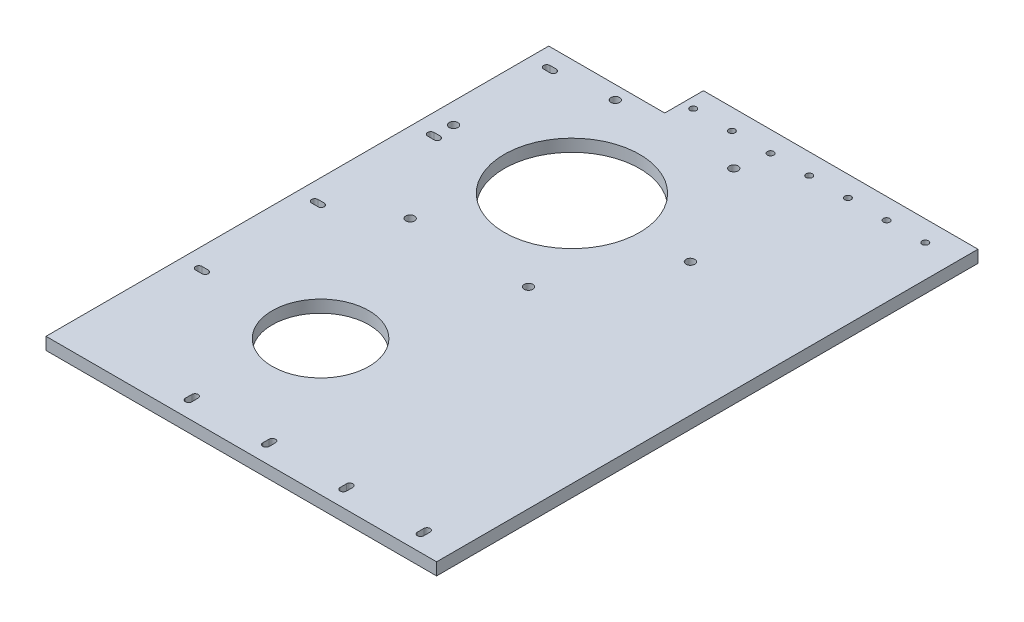
SolidWorks part; units mm, degrees
ref_plane "Front Plane" through (0, 0, 0) normal (0, 0, 1) x (1, 0, 0)
ref_plane "Top Plane" through (0, 0, 0) normal (0, 1, 0) x (1, 0, 0)
ref_plane "Right Plane" through (0, 0, 0) normal (1, 0, 0) x (0, 0, -1)
sketch "Sketch1" plane through (0, 0, 0) normal (0, 1, 0) x (1, 0, 0)
  line L3 (-71, 140) -> (71, 140)
  line L4 (71, -140) -> (71, 140)
  line L5 (0, 140) -> (0, -135) construction
  line L6 (0, 0) -> (71, 0) construction
  line L10 (-71, 140) -> (-71, 120)
  line L11 (-71, 120) -> (-131, 120)
  line L12 (-131, 120) -> (-131, -140)
  line L13 (-131, -140) -> (71, -140)
  point P0 (0, 0)
  dimension "D1" = 280
  dimension "D2" = 20
  dimension "D3" = 202
  dimension "D4" = 60
extrude "Boss-Extrude1" add sketch "Sketch1" along normal blind 6.35
sketch "Sketch2" plane through (0, 6.35, 0) normal (0, 1, 0) x (1, 0, 0)
  line L1 (0, 140) -> (0, -140) construction
  line L2 (71, 140) -> (-71, 140) construction
  line L3 (-131, -140) -> (71, -140) construction
  circle A0 centre (0, -65) radius 41.5 construction
  circle A1 centre (0, -23.5) radius 2.25
  circle A2 centre (29.3449, -35.6551) radius 2.25
  circle A3 centre (41.5, -65) radius 2.25
  circle A4 centre (29.3449, -94.3449) radius 2.25
  circle A5 centre (0, -106.5) radius 2.25
  circle A6 centre (-29.3449, -94.3449) radius 2.25
  circle A7 centre (-41.5, -65) radius 2.25
  circle A8 centre (-29.3449, -35.6551) radius 2.25
  circle A9 centre (0, -65) radius 80 construction
  circle A10 centre (0, -65) radius 30
  point P22 (0, -65)
  dimension "D1" = 83
  dimension "D2" = 4.5
  dimension "D4" = 160
  dimension "D6" = 60
  dimension "D5" = 75
  dimension "D3" = 8
extrude "Cut-Extrude1" [suppressed] cut sketch "Sketch2" against normal through all
sketch "Sketch6" [suppressed] plane through (0, 6.35, 0) normal (0, 1, 0) x (1, 0, 0)
  line L0 (0, -65) -> (-38.9712, -46.8274) construction
  line L1 (0, -65) -> (0, -23.5) construction
  line L2 (-40.9787, -51.1324) -> (-36.9638, -42.5225) construction
  line L3 (-36.9638, -42.5225) -> (-27.9007, -46.7486) construction
  circle A0 centre (0, -65) radius 30 construction
  circle A1 centre (-36.9638, -42.5225) radius 0.85
  circle A2 centre (-40.9787, -51.1324) radius 0.85
  circle A5 centre (-29.9082, -51.0536) radius 0.85
  point P7 (-38.9712, -46.8274)
  dimension "D4" = 1.7
  dimension "D5" = 10
  dimension "D7" = 10
  dimension "D6" = 1.7
  dimension "D1" = 43
  dimension "D2" = 9.5
  dimension "D3" = 65
extrude "Cut-Extrude5" [suppressed] cut sketch "Sketch6" against normal through all
sketch "Sketch8" [suppressed] plane through (0, 6.35, 0) normal (0, 1, 0) x (1, 0, 0)
  line L1 (71, 140) -> (-71, 140) construction
  line L2 (65, -20.6305) -> (65, 140) construction
  line L3 (71, -140) -> (71, 140) construction
  line L5 (45, 41.8036) -> (45, 140) construction
  circle A0 centre (0, 65) radius 25
  circle A1 centre (0, -65) radius 30 construction
  dimension "D1" = 130
  dimension "D2" = 50
  dimension "D3" = 6
  dimension "D4" = 20
extrude "Cut-Extrude9" [suppressed] cut sketch "Sketch8" against normal through all
sketch "Sketch9" plane through (0, 0, 0) normal (0, -1, 0) x (-1, 0, 0)
  circle A1 centre (45.6, 129.325) radius 1.65
  circle A2 centre (5.6, 129.325) radius 1.65
  circle A3 centre (-34.4, 129.325) radius 1.65
  circle A4 centre (65.6, 129.325) radius 1.65
  circle A5 centre (25.6, 129.325) radius 1.65
  circle A6 centre (-14.4, 129.325) radius 1.65
  circle A7 centre (-54.4, 129.325) radius 1.65
extrude "Cut-Extrude10" cut sketch "Sketch9" against normal blind 30
sketch "Sketch10" plane through (0, 0, 0) normal (0, -1, 0) x (1, 0, 0)
  line L0 (-121.975, 10) -> (-118.675, 10) construction
  line L3 (-121.975, 11.65) -> (-118.675, 11.65)
  line L4 (-121.975, 8.35) -> (-118.675, 8.35)
  line L5 (-121.975, 70) -> (-118.675, 70) construction
  line L6 (-121.975, 71.65) -> (-118.675, 71.65)
  line L7 (-121.975, 68.35) -> (-118.675, 68.35)
  line L8 (-121.975, -50) -> (-118.675, -50) construction
  line L9 (-121.975, -48.35) -> (-118.675, -48.35)
  line L10 (-121.975, -51.65) -> (-118.675, -51.65)
  line L11 (-121.975, -110) -> (-118.675, -110) construction
  line L12 (-121.975, -108.35) -> (-118.675, -108.35)
  line L13 (-121.975, -111.65) -> (-118.675, -111.65)
  circle A0 centre (-120.325, -110) radius 1.65
  circle A1 centre (-120.325, -50) radius 1.65
  circle A2 centre (-120.325, 10) radius 1.65
  circle A3 centre (-120.325, 70) radius 1.65
  arc A6 (-121.975, 11.65) -> (-121.975, 8.35) centre (-121.975, 10) ccw
  arc A7 (-118.675, 8.35) -> (-118.675, 11.65) centre (-118.675, 10) ccw
  arc A8 (-121.975, 71.65) -> (-121.975, 68.35) centre (-121.975, 70) ccw
  arc A9 (-118.675, 68.35) -> (-118.675, 71.65) centre (-118.675, 70) ccw
  arc A10 (-121.975, -48.35) -> (-121.975, -51.65) centre (-121.975, -50) ccw
  arc A11 (-118.675, -51.65) -> (-118.675, -48.35) centre (-118.675, -50) ccw
  arc A12 (-121.975, -108.35) -> (-121.975, -111.65) centre (-121.975, -110) ccw
  arc A13 (-118.675, -111.65) -> (-118.675, -108.35) centre (-118.675, -110) ccw
  point P14 (-120.325, 10)
  point P21 (-120.325, 70)
  point P28 (-120.325, -50)
  point P35 (-120.325, -110)
  dimension "D1" = 3.3
  dimension "D2" = 3.3
  dimension "D3" = 3.3
  dimension "D4" = 3.3
  dimension "D5" = 1.65
  dimension "D6" = 1.65
  dimension "D7" = 1.65
  dimension "D8" = 1.65
sketch "Sketch11" plane through (0, 6.35, 0) normal (0, 1, 0) x (1, 0, 0)
  line L0 (71, -127.15) -> (-131, -127.15) construction
  line L1 (71, -140) -> (71, 140) construction
  line L2 (456.625, -127.15) -> (-127.825, -127.15) construction
  line L3 (-131, 120) -> (-131, -140) construction
  line L4 (71, -132.85) -> (-131, -132.85) construction
  line L5 (456.625, -132.85) -> (-127.825, -132.85) construction
  line L6 (-65.6, 129.325) -> (-65.6, -130.005) construction
  line L7 (-65.6, -130.005) -> (71, -130) construction
  line L8 (456.625, -130) -> (-127.825, -130) construction
  line L9 (-25.6, 129.325) -> (-25.6, -130.0035) construction
  line L10 (14.4, 129.325) -> (14.4, -130.0021) construction
  line L11 (54.4, 129.325) -> (54.4, -130.0006) construction
  line L12 (-65.6, -128.355) -> (-65.6, -131.655) construction
  line L13 (-63.95, -128.355) -> (-63.95, -131.655)
  line L14 (-67.25, -128.355) -> (-67.25, -131.655)
  line L15 (-25.6, -128.3535) -> (-25.6, -131.6535) construction
  line L16 (-23.95, -128.3535) -> (-23.95, -131.6535)
  line L17 (-27.25, -128.3535) -> (-27.25, -131.6535)
  line L18 (14.4, -128.3521) -> (14.4, -131.6521) construction
  line L19 (16.05, -128.3521) -> (16.05, -131.6521)
  line L20 (12.75, -128.3521) -> (12.75, -131.6521)
  line L21 (54.4, -128.3506) -> (54.4, -131.6506) construction
  line L22 (56.05, -128.3506) -> (56.05, -131.6506)
  line L23 (52.75, -128.3506) -> (52.75, -131.6506)
  circle A0 centre (-65.6, -130.005) radius 1.65 construction
  circle A1 centre (-25.6, -130.0035) radius 1.65 construction
  circle A2 centre (14.4, -130.0021) radius 1.65 construction
  circle A3 centre (54.4, -130.0006) radius 1.65 construction
  arc A4 (-63.95, -128.355) -> (-67.25, -128.355) centre (-65.6, -128.355) ccw
  arc A5 (-67.25, -131.655) -> (-63.95, -131.655) centre (-65.6, -131.655) ccw
  arc A6 (-23.95, -128.3535) -> (-27.25, -128.3535) centre (-25.6, -128.3535) ccw
  arc A7 (-27.25, -131.6535) -> (-23.95, -131.6535) centre (-25.6, -131.6535) ccw
  arc A8 (16.05, -128.3521) -> (12.75, -128.3521) centre (14.4, -128.3521) ccw
  arc A9 (12.75, -131.6521) -> (16.05, -131.6521) centre (14.4, -131.6521) ccw
  arc A10 (56.05, -128.3506) -> (52.75, -128.3506) centre (54.4, -128.3506) ccw
  arc A11 (52.75, -131.6506) -> (56.05, -131.6506) centre (54.4, -131.6506) ccw
  point P33 (-65.6, -130.005)
  point P39 (-25.6, -130.0035)
  point P46 (14.4, -130.0021)
  point P53 (54.4, -130.0006)
  dimension "D2" = 3.3
  dimension "D1" = 259.33
extrude "Cut-Extrude12" cut sketch "Sketch11" against normal blind 30
extrude "Cut-Extrude13" cut sketch "Sketch10" against normal blind 10 contours A0 | L13 A13 L12 A0 | L12 A12 L13 A0 | L9 A10 L10 A1 | A1 | L10 A11 L9 A1 | L3 A6 L4 A2 | A2 | L4 A7 L3 A2 | L6 A8 L7 A3 | A3 | L7 A9 L6 A3 region at (-122.4459, 0, 10) region at (-118.2041, 0, 10) region at (-120.325, 0, 10) region at (-122.4459, 0, 70) region at (-118.2041, 0, 70) region at (-120.325, 0, 70) region at (-122.4459, 0, -50) region at (-118.2041, 0, -50) region at (-120.325, 0, -50) region at (-122.4459, 0, -110) region at (-118.2041, 0, -110) region at (-120.325, 0, -110)
sketch "Sketch12" plane through (0, 6.35, 0) normal (0, 1, 0) x (1, 0, 0)
  line L0 (-131, -140) -> (71, -140) construction
  line L1 (71, -140) -> (71, 140) construction
  circle A0 centre (-59, 60) radius 35
  dimension "D1" = 70
  dimension "D2" = 200
  dimension "D3" = 130
extrude "Cut-Extrude14" cut sketch "Sketch12" against normal through all
sketch "Sketch13" plane through (0, 6.35, 0) normal (0, 1, 0) x (1, 0, 0)
  line L0 (-126.5, 60) -> (-114, 60) construction
  circle A2 centre (-59, 60) radius 67.5 construction
  circle A3 centre (-120.25, 60) radius 2.25
  circle A4 centre (-89.625, 113.0441) radius 2.25
  circle A5 centre (-59, 60) radius 67.5 construction
  circle A6 centre (-28.375, 113.0441) radius 2.25
  circle A7 centre (-59, 60) radius 67.5 construction
  circle A8 centre (2.25, 60) radius 2.25
  circle A9 centre (-59, 60) radius 67.5 construction
  circle A10 centre (-28.375, 6.9559) radius 2.25
  circle A11 centre (-59, 60) radius 67.5 construction
  circle A12 centre (-89.625, 6.9559) radius 2.25
  circle A13 centre (-59, 60) radius 67.5 construction
  circle A14 centre (-59, 60) radius 55 construction
  circle A15 centre (-59, 60) radius 35 construction
  point P25 (-59, 60)
  dimension "D1" = 135
  dimension "D2" = 4.5
  dimension "D3" = 6
  dimension "D4" = 110
extrude "Cut-Extrude15" cut sketch "Sketch13" against normal through all
sketch "Sketch14" plane through (0, 6.35, 0) normal (0, 1, 0) x (1, 0, 0)
  circle A0 centre (-59, -70) radius 25
  circle A1 centre (-59, 60) radius 35 construction
  circle A2 centre (-59, 60) radius 35 construction
  point P5 (0, 0)
  dimension "D1" = 50
  dimension "D2" = 130
extrude "Cut-Extrude16" cut sketch "Sketch14" against normal blind 10
